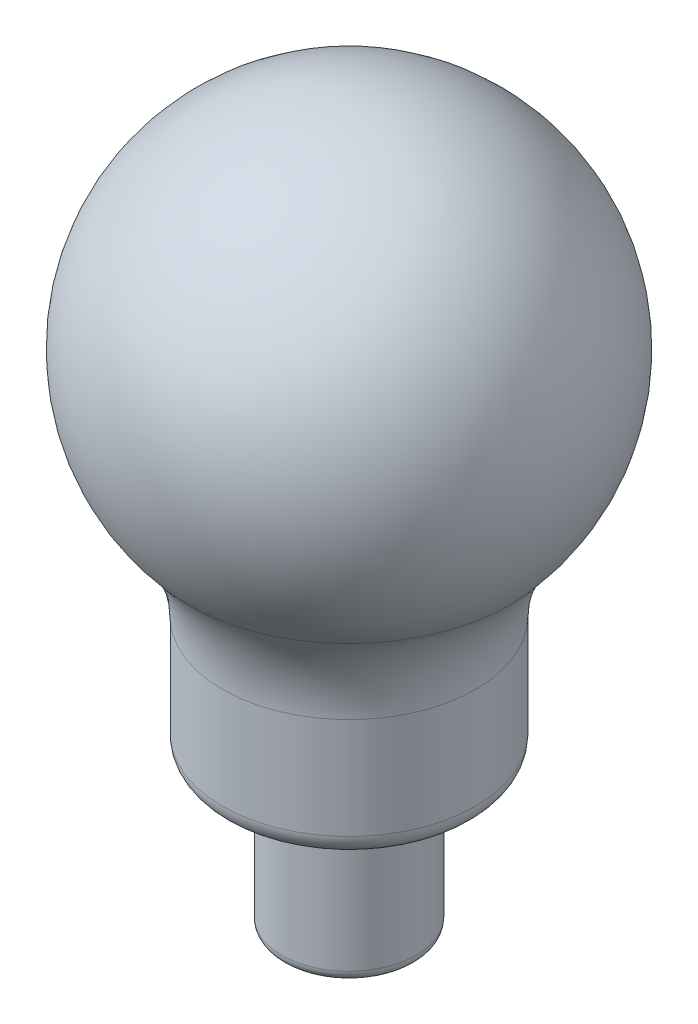
SolidWorks part; units mm, degrees
ref_plane "Front Plane" through (0, 0, 0) normal (0, 0, 1) x (1, 0, 0)
ref_plane "Top Plane" through (0, 0, 0) normal (0, 1, 0) x (1, 0, 0)
ref_plane "Right Plane" through (0, 0, 0) normal (1, 0, 0) x (0, 0, -1)
sketch "Sketch1" plane through (0, 0, 0) normal (0, 1, 0) x (1, 0, 0)
  circle A0 centre (7.5, 0) radius 0.5
extrude "Boss-Extrude1" add sketch "Sketch1" along normal blind 50
sketch "Sketch2" plane through (0, 0, 0) normal (0, 1, 0) x (1, 0, 0)
  circle A0 centre (-7.5, 0) radius 0.5
extrude "Boss-Extrude2" add sketch "Sketch2" along normal blind 50
sketch "Sketch3" plane through (0, 0, 0) normal (1, 0, 0) x (0, 0, -1)
  circle A0 centre (0, 49.097) radius 0.048
extrude "Boss-Extrude3" add sketch "Sketch3" along normal blind 7.7 and the other way blind 7.7
sketch "Sketch4" plane through (0, 0, 0) normal (0, 0, 1) x (1, 0, 0)
  line L0 (-14.9728, 9.9416) -> (-9.973, 9.9416)
  line L1 (0, 100) -> (0, -20) construction
  line L2 (-17.4728, 26.8973) -> (-17.4728, 12.4416)
  line L3 (-18.0728, 26.8973) -> (-18.0728, 12.4416)
  line L4 (-14.9728, 9.3416) -> (-9.973, 9.3416)
  line L5 (-9.573, 8.9416) -> (-9.573, -10.2513)
  line L6 (-8.973, 8.9416) -> (-8.973, -10.2513)
  line L7 (0, 90.6) -> (0, 90)
  line L8 (-7.973, -11.2513) -> (-7.973, -11.8513)
  arc A0 (0, 90) -> (-22.4837, 40.1384) centre (0, 60) ccw
  arc A1 (0, 90.6) -> (-22.9334, 39.7412) centre (0, 60) ccw
  arc A2 (-17.4728, 26.8973) -> (-22.4837, 40.1384) centre (-37.4728, 26.8973) ccw
  arc A3 (-18.0728, 26.8973) -> (-22.9334, 39.7412) centre (-37.4728, 26.8973) ccw
  arc A4 (-17.4728, 12.4416) -> (-14.9728, 9.9416) centre (-14.9728, 12.4416) ccw
  arc A5 (-18.0728, 12.4416) -> (-14.9728, 9.3416) centre (-14.9728, 12.4416) ccw
  arc A6 (-8.973, 8.9416) -> (-9.973, 9.9416) centre (-9.973, 8.9416) ccw
  arc A7 (-9.573, 8.9416) -> (-9.973, 9.3416) centre (-9.973, 8.9416) ccw
  arc A8 (-8.973, -10.2513) -> (-7.973, -11.2513) centre (-7.973, -10.2513) ccw
  arc A9 (-9.573, -10.2513) -> (-7.973, -11.8513) centre (-7.973, -10.2513) ccw
  point P19 (14.7674, 9.9416)
  dimension "D1" = 0.6
revolve "Revolve1" add sketch "Sketch4" angle 360 about L1
